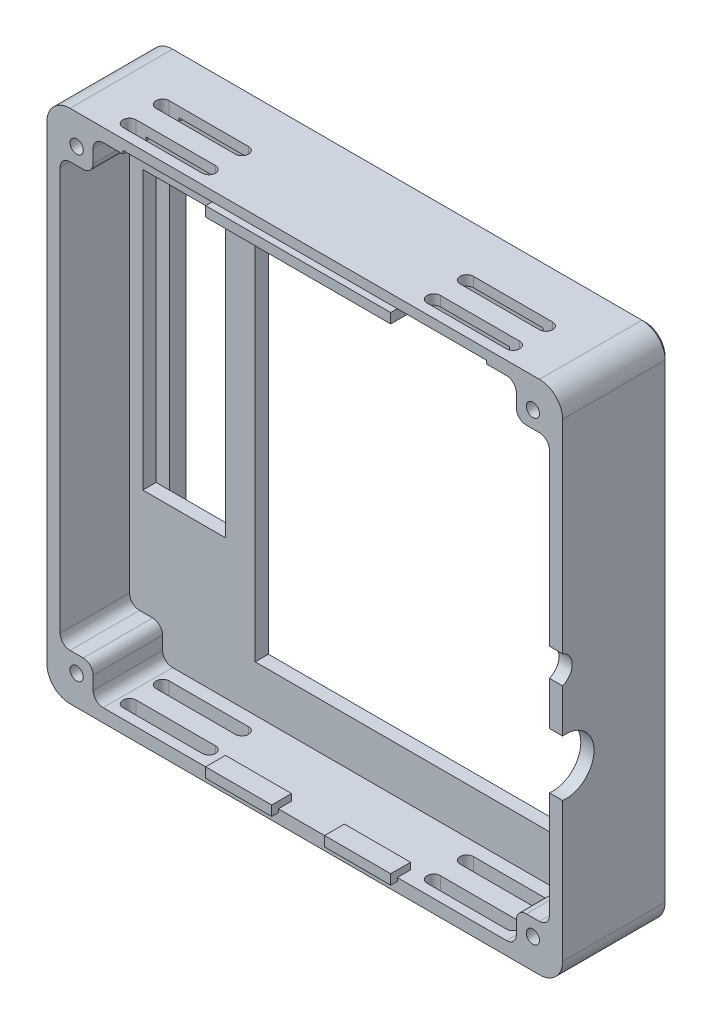
SolidWorks part; units mm, degrees
ref_plane "前视基准面" through (0, 0, 0) normal (0, 0, 1) x (1, 0, 0)
ref_plane "上视基准面" through (0, 0, 0) normal (0, 1, 0) x (1, 0, 0)
ref_plane "右视基准面" through (0, 0, 0) normal (1, 0, 0) x (0, 0, -1)
other "Configuration Table"
sketch "草图1" plane through (0, 0, 0) normal (0, 0, 1) x (1, 0, 0)
  line L1 (-39, -39) -> (39, -39)
  line L2 (-39, -39) -> (-39, 39)
  line L3 (-39, 39) -> (39, 39)
  line L4 (39, -39) -> (39, 39)
  line L5 (-39, -39) -> (39, 39) construction
  line L6 (-39, 39) -> (39, -39) construction
  point P0 (0, 0)
  dimension "D1" = 78
extrude "凸台-拉伸1" add sketch "草图1" along normal blind 5.5
sketch "草图2" plane through (0, 0, 5.5) normal (0, 0, 1) x (1, 0, 0)
  line L1 (-39, -39) -> (39, -39)
  line L2 (-39, -39) -> (-39, 39)
  line L3 (-39, 39) -> (39, 39)
  line L4 (39, -39) -> (39, 39)
  line L5 (-39, -39) -> (39, 39) construction
  line L6 (-39, 39) -> (39, -39) construction
  line L7 (37, 37) -> (-37, 37)
  line L8 (37, 37) -> (37, -37)
  line L9 (37, -37) -> (-37, -37)
  line L10 (-37, 37) -> (-37, -37)
  line L11 (37, 37) -> (-37, -37) construction
  line L12 (37, -37) -> (-37, 37) construction
  line L13 (-37, 37) -> (-32, 37)
  line L14 (-37, 37) -> (-37, 32)
  line L15 (-37, 32) -> (-32, 32)
  line L16 (-32, 37) -> (-32, 32)
  line L17 (37, 37) -> (32, 37)
  line L18 (37, 37) -> (37, 32)
  line L19 (37, 32) -> (32, 32)
  line L20 (32, 37) -> (32, 32)
  line L21 (-37, -37) -> (-32, -37)
  line L22 (-37, -37) -> (-37, -32)
  line L23 (-37, -32) -> (-32, -32)
  line L24 (-32, -37) -> (-32, -32)
  line L25 (37, -37) -> (32, -37)
  line L26 (37, -37) -> (37, -32)
  line L27 (37, -32) -> (32, -32)
  line L28 (32, -37) -> (32, -32)
  point P0 (0, 0)
  point P7 (0, 0)
  line M22 (39, -39) -> (39, 39)
  line M23 (39, 39) -> (-39, 39)
  line M24 (-39, 39) -> (-39, -39)
  line M25 (-39, -39) -> (39, -39)
  dimension "D1" = 2
  dimension "D2" = 5
extrude "凸台-拉伸2" add sketch "草图2" along normal blind 10.5 contours L10 L7 L8 L9 M25 M22 M23 M24 | L16 L7 L10 L15 | L7 L20 L19 L8 | L28 L9 L8 L27 | L9 L24 L23 L10 region at (-37.8969, 0, 5.5) region at (34.5, 34.5, 5.5) region at (-34.5, 34.5, 5.5) region at (34.5, -34.5, 5.5) region at (-34.5, -34.5, 5.5)
fillet "圆角1" radius 1.5 12 edges at (37, 32, 10.75) (32, 32, 10.75) (32, 37, 10.75) (37, -32, 10.75) (32, -32, 10.75) (32, -37, 10.75) (-32, -37, 10.75) (-32, -32, 10.75) (-37, -32, 10.75) (-37, 32, 10.75) (-32, 37, 10.75) (-32, 32, 10.75)
fillet "圆角2" radius 3.5 4 edges at (-39, 39, 8) (39, 39, 8) (39, -39, 8) (-39, -39, 8)
sketch "草图3" plane through (0, 0, 0) normal (0, 0, -1) x (-1, 0, 0)
  line L8 (37.5, -35.5) -> (37.5, 35.5)
  line L9 (-35.5, -37.5) -> (35.5, -37.5)
  line L10 (-37.5, 35.5) -> (-37.5, -35.5)
  line L11 (35.5, 37.5) -> (-35.5, 37.5)
  line L12 (37.5, -35.5) -> (37.5, 35.5)
  line L13 (-35.5, -37.5) -> (35.5, -37.5)
  line L14 (-37.5, 35.5) -> (-37.5, -35.5)
  line L15 (35.5, 37.5) -> (-35.5, 37.5)
  arc A8 (37.5, 35.5) -> (35.5, 37.5) centre (35.5, 35.5) ccw
  arc A9 (35.5, -37.5) -> (37.5, -35.5) centre (35.5, -35.5) ccw
  arc A10 (-37.5, -35.5) -> (-35.5, -37.5) centre (-35.5, -35.5) ccw
  arc A11 (-35.5, 37.5) -> (-37.5, 35.5) centre (-35.5, 35.5) ccw
  arc A12 (37.5, 35.5) -> (35.5, 37.5) centre (35.5, 35.5) ccw
  arc A13 (35.5, -37.5) -> (37.5, -35.5) centre (35.5, -35.5) ccw
  arc A14 (-37.5, -35.5) -> (-35.5, -37.5) centre (-35.5, -35.5) ccw
  arc A15 (-35.5, 37.5) -> (-37.5, 35.5) centre (-35.5, 35.5) ccw
  dimension "D1" = 1.5
extrude "切除-拉伸1" cut sketch "草图3" against normal blind 1
sketch "草图4" plane through (0, 0, 1) normal (0, 0, -1) x (-1, 0, 0)
  line L0 (35.5, 37.5) -> (-35.5, 37.5) construction
  line L1 (-32.95, 37.5) -> (32.95, 37.5)
  line L2 (-32.95, 37.5) -> (-32.95, -33)
  line L3 (-32.95, -33) -> (32.95, -33)
  line L4 (32.95, 37.5) -> (32.95, -33)
  line L6 (0, 0) -> (0, 26.6317) construction
  line L7 (-32.95, 36.85) -> (32.95, 36.85)
  line L8 (27.5, 36.85) -> (27.5, 37.5)
  line L9 (-27.5, 36.85) -> (-27.5, 37.5)
  line M10 (35.5, 37.5) -> (-35.5, 37.5)
  dimension "D1" = 70.5
  dimension "D2" = 65.9
  dimension "D3" = 0.65
  dimension "D4" = 55
extrude "切除-拉伸2" cut sketch "草图4" against normal blind 2.5 contours L3 L6 L7 L2 | L6 L3 L4 L7 | L7 L6 L9 M10 | L6 L7 L8 L1 region at (0, 37.175, 1) region at (30.225, 35.8897, 1)
sketch "草图5" plane through (0, 0, 1) normal (0, 0, -1) x (-1, 0, 0)
  line L0 (-35.5, 39) -> (35.5, 39) construction
  line L1 (-34.5, -34.5) -> (34.5, -34.5) construction
  line L2 (-34.5, -34.5) -> (-34.5, 34.5) construction
  line L3 (-34.5, 34.5) -> (34.5, 34.5) construction
  line L4 (34.5, -34.5) -> (34.5, 34.5) construction
  line L5 (-34.5, -34.5) -> (34.5, 34.5) construction
  line L6 (-34.5, 34.5) -> (34.5, -34.5) construction
  circle A0 centre (-34.5, 34.5) radius 1
  circle A1 centre (34.5, 34.5) radius 1
  circle A2 centre (34.5, -34.5) radius 1
  circle A3 centre (-34.5, -34.5) radius 1
  point P0 (0, 0)
  dimension "D2" = 2
  dimension "D1" = 4.5
extrude "切除-拉伸3" cut sketch "草图5" against normal through all
chamfer "倒角1" distance 0.5 angle 45 8 edges at (-39, 0, 0) (-37.9749, -37.9749, 0) (-37.9749, 37.9749, 0) (0, -39, 0) (0, 39, 0) (37.9749, -37.9749, 0) (37.9749, 37.9749, 0) (39, 0, 0)
sketch "草图6" plane through (0, 0, 3.5) normal (0, 0, -1) x (-1, 0, 0)
  line L1 (-27.5, 37.5) -> (27.5, 37.5)
  line L2 (-27.5, 37.5) -> (-27.5, 35.5)
  line L3 (-27.5, 35.5) -> (27.5, 35.5)
  line L4 (27.5, 37.5) -> (27.5, 35.5)
  line L5 (-36, 28) -> (18, 28)
  line L6 (-36, 28) -> (-36, -30)
  line L7 (-36, -30) -> (18, -30)
  line L8 (18, 28) -> (18, -30)
  line L9 (22.5, 26) -> (35, 26)
  line L10 (22.5, 26) -> (22.5, -16)
  line L11 (22.5, -16) -> (35, -16)
  line L12 (35, 26) -> (35, -16)
  dimension "D1" = 2
  dimension "D2" = 54
  dimension "D3" = 30
  dimension "D4" = 58
  dimension "D5" = 36
  dimension "D6" = 22.5
  dimension "D7" = 12.5
  dimension "D8" = 42
  dimension "D9" = 16
extrude "切除-拉伸4" cut sketch "草图6" against normal through all
sketch "草图7" plane through (0, 0, 16) normal (0, 0, 1) x (1, 0, 0)
  line L0 (-15.0283, 0) -> (15.498, 0) construction
  line L17 (0, -8.9343) -> (0, 15.7561) construction
  line L20 (35.5, -37.5) -> (-35.5, -37.5) construction
  line L21 (14, -37.5) -> (4, -37.5)
  line L22 (14, -37.5) -> (14, -36)
  line L23 (14, -36) -> (4, -36)
  line L24 (4, -37.5) -> (4, -36)
  line L25 (-27.5, 37.5) -> (27.5, 37.5) construction
  line L26 (-4, -37.5) -> (-14, -37.5)
  line L27 (-4, -37.5) -> (-4, -36)
  line L28 (-4, -36) -> (-14, -36)
  line L29 (-14, -37.5) -> (-14, -36)
  line L30 (-14, 37.5) -> (14, 37.5)
  line L31 (-14, 37.5) -> (-14, 36)
  line L32 (-14, 36) -> (14, 36)
  line L33 (14, 37.5) -> (14, 36)
  dimension "D1" = 1.5
  dimension "D2" = 28
  dimension "D4" = 1.5
  dimension "D5" = 28
  dimension "D6" = 8
extrude "凸台-拉伸3" add sketch "草图7" along normal blind 1 and the other way blind 2
sketch "草图8" plane through (39, 0, 0) normal (1, 0, 0) x (0, 0, -1)
  line L0 (-16, -35.5) -> (-0.5, -35.5) construction
  line L1 (-16, -35.5) -> (-16, 35.5) construction
  line L2 (-16, 4.8) -> (-16, 0.6) construction
  circle A0 centre (-15.5, -10.2) radius 4.25
  circle A1 centre (-16.8, 2.7) radius 2.2472
  dimension "D1" = 8.5
  dimension "D4" = 4.2
  dimension "D2" = 25.3
  dimension "D3" = 0.5
  dimension "D5" = 38.2
  dimension "D6" = 0.8
extrude "切除-拉伸5" cut sketch "草图8" against normal blind 10
sketch "草图9" plane through (0, -39, 0) normal (0, -1, 0) x (1, 0, 0)
  line L0 (-29, 13.5) -> (-17, 13.5) construction
  line L1 (-29, 14.5) -> (-17, 14.5)
  line L2 (-29, 12.5) -> (-17, 12.5)
  line L3 (-39, 0.5) -> (-39, 16) construction
  line L4 (-35.5, 16) -> (35.5, 16) construction
  line L5 (-29, 8.5) -> (-17, 8.5) construction
  line L6 (-29, 9.5) -> (-17, 9.5)
  line L7 (-29, 7.5) -> (-17, 7.5)
  line L8 (-29, 13.5) -> (-29, 8.5) construction
  line L9 (0, -1000) -> (0, 49000) construction
  line L10 (35.5, 0) -> (-35.5, 0) construction
  line L11 (29, 8.5) -> (17, 8.5) construction
  line L12 (29, 9.5) -> (17, 9.5)
  line L13 (29, 7.5) -> (17, 7.5)
  line L14 (29, 13.5) -> (17, 13.5) construction
  line L15 (29, 14.5) -> (17, 14.5)
  line L16 (29, 12.5) -> (17, 12.5)
  arc A0 (-29, 14.5) -> (-29, 12.5) centre (-29, 13.5) ccw
  arc A1 (-17, 12.5) -> (-17, 14.5) centre (-17, 13.5) ccw
  arc A2 (-29, 9.5) -> (-29, 7.5) centre (-29, 8.5) ccw
  arc A3 (-17, 7.5) -> (-17, 9.5) centre (-17, 8.5) ccw
  arc A4 (29, 9.5) -> (29, 7.5) centre (29, 8.5) cw
  arc A5 (17, 7.5) -> (17, 9.5) centre (17, 8.5) cw
  arc A6 (29, 14.5) -> (29, 12.5) centre (29, 13.5) cw
  arc A7 (17, 12.5) -> (17, 14.5) centre (17, 13.5) cw
  point P2 (-23, 13.5)
  point P15 (-23, 8.5)
  point P25 (0, 0)
  point P27 (23, 8.5)
  point P34 (23, 13.5)
  dimension "D3" = 1
  dimension "D1" = 12
  dimension "D2" = 10
  dimension "D4" = 2.5
  dimension "D6" = 5
  dimension "D5" = 2
extrude "切除-拉伸6" cut sketch "草图9" against normal through all
